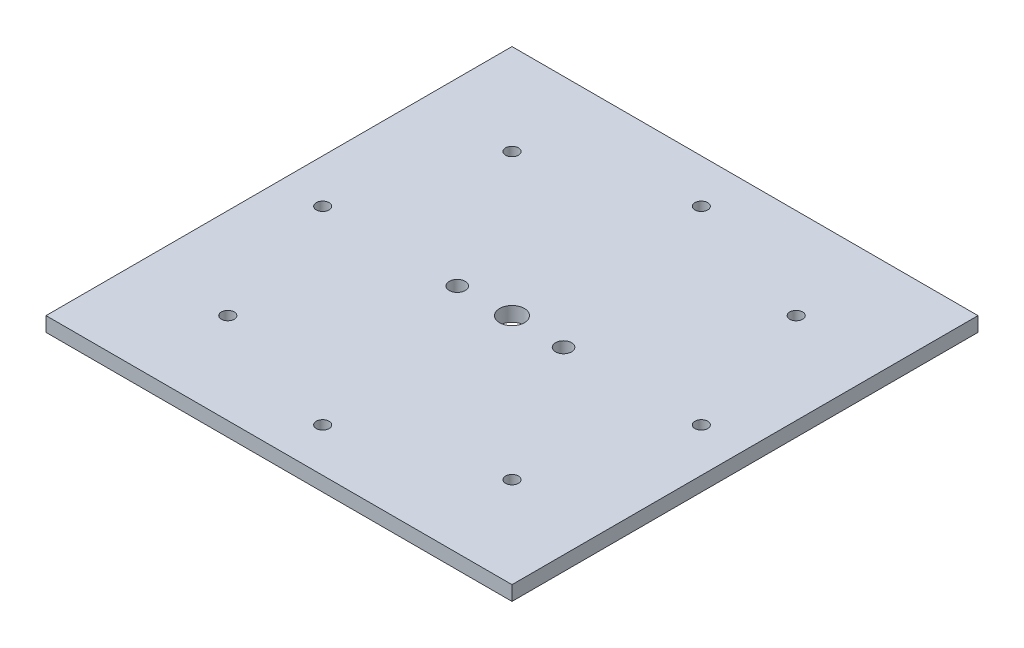
SolidWorks part; units mm, degrees
ref_plane "Front Plane" through (0, 0, 0) normal (0, 0, 1) x (1, 0, 0)
ref_plane "Top Plane" through (0, 0, 0) normal (0, 1, 0) x (1, 0, 0)
ref_plane "Right Plane" through (0, 0, 0) normal (1, 0, 0) x (0, 0, -1)
sketch "Sketch1" plane through (0, 0, 0) normal (0, 1, 0) x (1, 0, 0)
  line L0 (0, 80) -> (0, -80) construction
  line L1 (-80, 80) -> (80, 80)
  line L2 (-80, 80) -> (-80, -80)
  line L3 (-80, -80) -> (80, -80)
  line L4 (80, 80) -> (80, -80)
  line L5 (-80, 80) -> (80, -80) construction
  line L6 (-80, -80) -> (80, 80) construction
  circle A0 centre (0, 0) radius 69 construction
  circle A2 centre (48.7904, 48.7904) radius 2.2
  circle A4 centre (48.7904, -48.7904) radius 2.2
  circle A6 centre (-48.7904, -48.7904) radius 2.2
  circle A8 centre (-48.7904, 48.7904) radius 2.2
  circle A9 centre (0, 0) radius 4.25
  circle A10 centre (18.2724, -0.5716) radius 2.75
  circle A11 centre (-18.2276, -0.5716) radius 2.75
  circle A12 centre (0, 0) radius 65 construction
  circle A13 centre (0, 65) radius 2.2
  circle A14 centre (65, 0) radius 2.2
  circle A15 centre (0, -65) radius 2.2
  circle A16 centre (-65, 0) radius 2.2
  point P0 (0, 0)
  point P13 (0, 0)
  point P16 (0, 0)
  point P19 (0, 0)
  point P22 (0, 0)
  point P25 (0, 0)
  point P28 (0, 0)
  point P31 (0, 0)
  point P34 (0, 0)
  point P43 (0, 0)
  dimension "D3" = 8
  dimension "D4" = 4
  dimension "D1" = 160
  dimension "D2" = 160
extrude "Boss-Extrude1" add sketch "Sketch1" along normal blind 5
